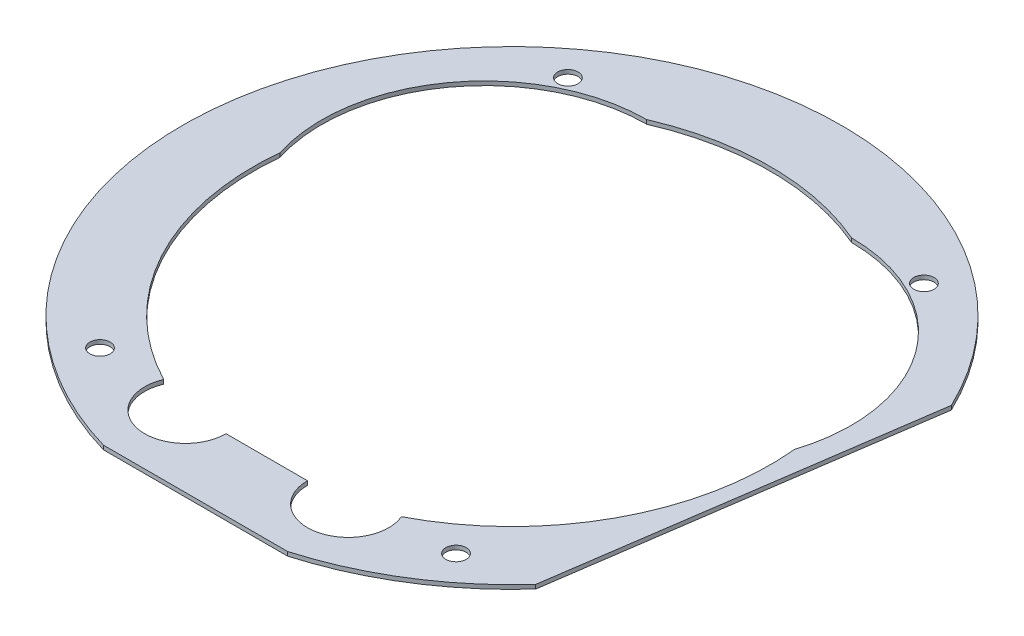
SolidWorks part; units mm, degrees
ref_plane "Front Plane" through (0, 0, 0) normal (0, 0, 1) x (1, 0, 0)
ref_plane "Top Plane" through (0, 0, 0) normal (0, 1, 0) x (1, 0, 0)
ref_plane "Right Plane" through (0, 0, 0) normal (1, 0, 0) x (0, 0, -1)
sketch "Sketch1" plane through (0, 0, 0) normal (0, 1, 0) x (1, 0, 0)
  line L1 (-4, -24.1073) -> (4, -24.1073)
  line L2 (29.2378, 13.961) -> (24.0491, -21.7118)
  line L3 (-9.0608, -31.1073) -> (9.0608, -31.1073)
  arc A0 (11.6854, -22.5524) -> (25.2782, 2.484) centre (0, 0) ccw
  circle A1 centre (-17.5, 23) radius 1
  arc A2 (9.0608, -31.1073) -> (24.0491, -21.7118) centre (0, 0) ccw
  arc A3 (29.2378, 13.961) -> (-9.0608, -31.1073) centre (0, 0) ccw
  circle A4 centre (-17.5, -23) radius 1
  circle A5 centre (17.5, -23) radius 1
  circle A6 centre (17.5, 23) radius 1
  arc A7 (-4, -24.1073) -> (-11.6854, -22.5524) centre (-8, -24.1073) cw
  arc A8 (4, -24.1073) -> (11.6854, -22.5524) centre (8, -24.1073) ccw
  arc A9 (-25.2782, 2.484) -> (-10.0702, 23.3185) centre (-10.0261, 7.3185) cw
  arc A10 (10.0702, 23.3185) -> (25.2782, 2.484) centre (10.0261, 7.3185) cw
  arc A11 (-25.2782, 2.484) -> (-11.6854, -22.5524) centre (0, 0) ccw
  arc A12 (10.0702, 23.3185) -> (-10.0702, 23.3185) centre (0, 0) ccw
  dimension "D1" = 2
  dimension "D2" = 2
  dimension "D3" = 2
  dimension "D4" = 2
  dimension "D10" = 7
  dimension "D11" = 25.4
  dimension "D12" = 32.4
  dimension "D15" = 4
  dimension "D16" = 4
  dimension "D20" = 30
  dimension "D21" = 16
  dimension "D22" = 16
  dimension "D5" = 17.5
  dimension "D6" = 23
  dimension "D7" = 46
  dimension "D8" = 35
  dimension "D9" = 7
  dimension "D13" = 16
  dimension "D14" = 36.0481
  dimension "D17" = 8
  dimension "D18" = 7.8411
  dimension "D19" = 7.8411
  dimension "D23" = 30
extrude "Boss-Extrude1" add sketch "Sketch1" along normal blind 0.4
